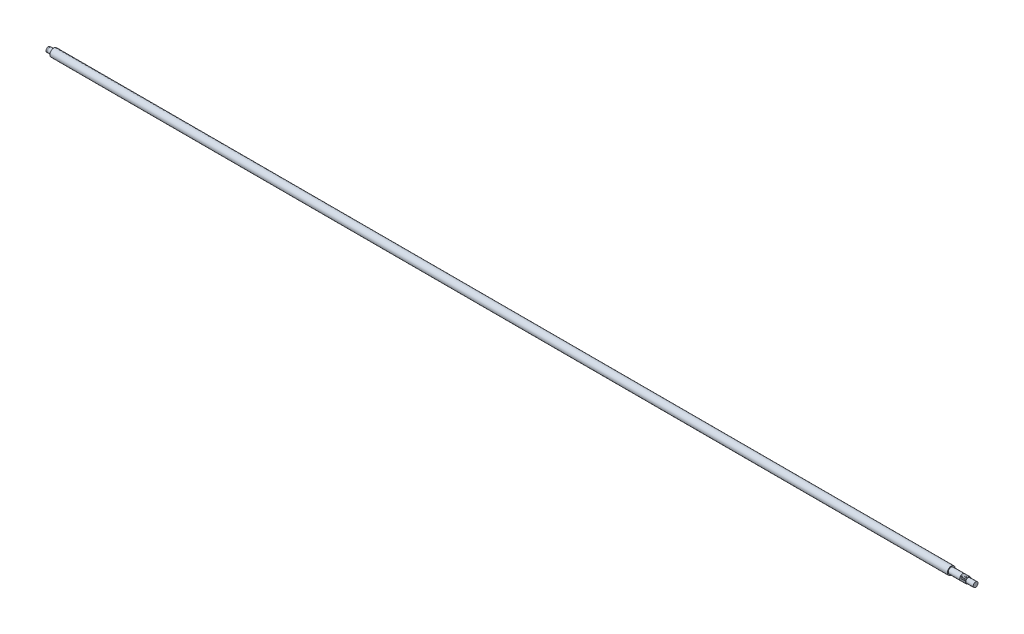
SolidWorks part; units mm, degrees
material "Хромистая нержавеющая сталь"
ref_plane "Спереди" through (0, 0, 0) normal (0, 0, 1) x (1, 0, 0)
ref_plane "Сверху" through (0, 0, 0) normal (0, 1, 0) x (1, 0, 0)
ref_plane "Справа" through (0, 0, 0) normal (1, 0, 0) x (0, 0, -1)
sketch "Эскиз1" plane through (0, 0, 0) normal (0, 0, 1) x (1, 0, 0)
  line L0 (-1810.0019, 5.9419) -> (-1810.0019, 10.8919)
  line L1 (-1810.0019, 10.8919) -> (-1808.0519, 10.8919)
  line L2 (-1808.0519, 10.8919) -> (-1808.0519, 10.7419)
  line L3 (-1808.0519, 10.7419) -> (-1806.9019, 10.7419)
  line L4 (-1806.9019, 10.7419) -> (-1806.9019, 10.8919)
  line L5 (-1806.9019, 10.8919) -> (-1799.0019, 10.8919)
  line L6 (-1799.0019, 10.8919) -> (-1799.0019, 13.9419)
  line L7 (-1799.0019, 13.9419) -> (39.9981, 13.9419)
  line L8 (39.9981, 13.9419) -> (39.9981, 11.9419)
  line L9 (39.9981, 11.9419) -> (74.9981, 11.9419)
  line L10 (74.9981, 11.9419) -> (74.9981, 10.8919)
  line L11 (74.9981, 10.8919) -> (89.9981, 10.8919)
  line L12 (89.9981, 10.8919) -> (89.9981, 5.9419)
  line L13 (89.9981, 5.9419) -> (-1810.0019, 5.9419)
  line L14 (60.9981, 14.6846) -> (60.9981, -1.3142) construction
  dimension "D1" = 1.15
  dimension "D2" = 7.9
  dimension "D3" = 11
  dimension "D4" = 35
  dimension "D5" = 50
  dimension "D6" = 14
  dimension "D7" = 4.95
  dimension "D8" = 1.05
  dimension "D9" = 2
  dimension "D10" = 4.95
  dimension "D11" = 4.8
  dimension "D12" = 4.95
  dimension "D13" = 1900
revolve "Повернуть1" add sketch "Эскиз1" angle 360 about L13
ref_plane "Плоскость1" through (49.9981, 0, 0) normal (1, 0, 0) x (0, 0, -1)
sketch "Эскиз2" plane through (49.9981, 0, 0) normal (1, 0, 0) x (0, 0, -1)
  circle A0 centre (0, 5.9419) radius 8 construction
  circle A1 centre (0, 5.9419) radius 8
curve "Спираль1" pitch 5 height 290 turns 58
sketch "Эскиз3" plane through (0, 0, 0) normal (0, 0, 1) x (1, 0, 0)
  line L0 (-207.8405, -2.5666) -> (-201.4949, -2.5666) construction
  line L1 (-210.2778, -2.0666) -> (-203.5838, -2.0666) construction
  line L2 (-207.8405, -4.8575) -> (-207.8405, -1.8666) construction
  line L3 (-205.3405, -4.8575) -> (-205.3405, -0.2923) construction
  line L4 (-205.3405, -1.8666) -> (-205.4905, -2.0666)
  line L5 (-205.4905, -2.0666) -> (-205.4905, -2.5666)
  line L6 (-205.4905, -2.5666) -> (-205.1905, -2.5666)
  line L7 (-205.1905, -2.5666) -> (-205.1905, -2.0666)
  line L8 (-205.1905, -2.0666) -> (-205.3405, -1.8666)
  circle A0 centre (-207.8405, -2.5666) radius 1.5875
  point P7 (-207.7498, -2.0666)
  dimension "D1" = 3.175
  dimension "D2" = 0.5
  dimension "D3" = 2.5
  dimension "D4" = 0.2
  dimension "D5" = 0.3
ref_plane "Плоскость2" through (84.9981, 0, 0) normal (1, 0, 0) x (0, 0, -1)
sketch "Эскиз4" plane through (84.9981, 0, 0) normal (1, 0, 0) x (0, 0, -1)
  circle A0 centre (0, 5.9419) radius 6 construction
  circle A1 centre (0, 5.9419) radius 6
curve "Спираль2" pitch 1 height 22 radius 6 centre (84.9981, 5.9419, 0) axis (-1, 0, 0) start towards (0, 0, 1)
sketch "Эскиз5" plane through (0, 0, 0) normal (0, 0, 1) x (1, 0, 0)
  line L0 (76.2561, 0.4419) -> (75.7561, -0.0581)
  line L1 (39.9981, -0.0581) -> (74.9981, -0.0581) construction
  line L2 (75.7561, -0.0581) -> (75.7561, -1.0581)
  line L3 (75.7561, -1.0581) -> (76.7561, -1.0581)
  line L4 (76.7561, -1.0581) -> (76.7561, -0.0581)
  line L5 (76.7561, -0.0581) -> (76.2561, 0.4419)
  line L6 (76.2561, 0.4419) -> (76.2561, -0.2584) construction
  line L7 (75.7561, -0.0581) -> (76.7561, -0.0581) construction
  dimension "D1" = 0.5
  dimension "D2" = 1
  dimension "D3" = 1
sweep "Вырез-По траектории7" cut profiles "Эскиз5" path "Спираль2" align with end faces yes
